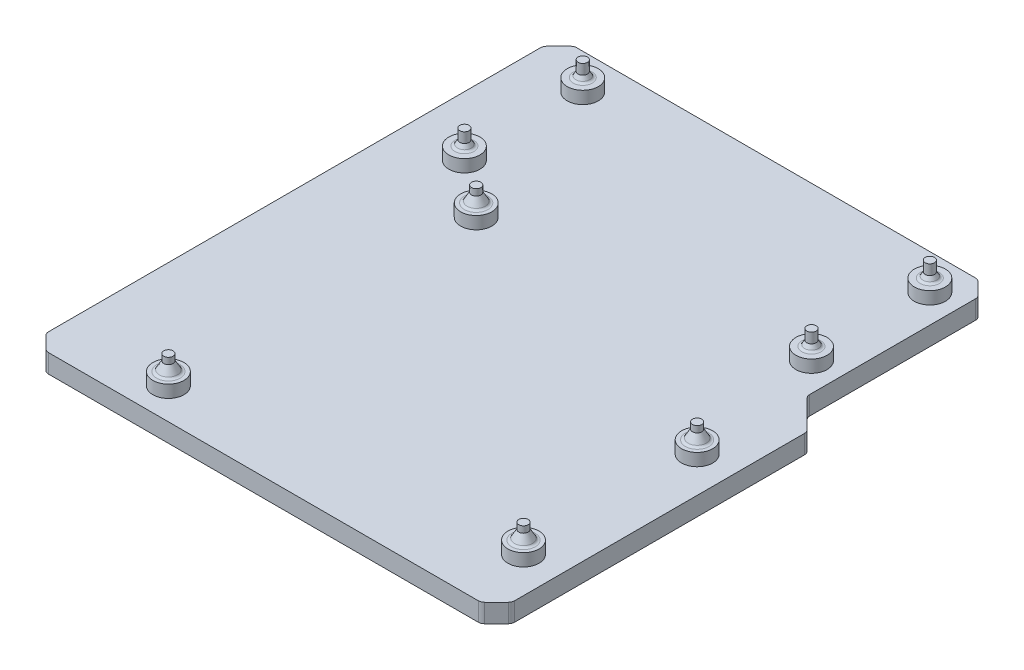
SolidWorks part; units mm, degrees
ref_plane "Front Plane" through (0, 0, 0) normal (0, 0, 1) x (1, 0, 0)
ref_plane "Top Plane" through (0, 0, 0) normal (0, 1, 0) x (1, 0, 0)
ref_plane "Right Plane" through (0, 0, 0) normal (1, 0, 0) x (0, 0, -1)
sketch "Sketch1" plane through (0, 0, 0) normal (0, 1, 0) x (1, 0, 0)
  line L1 (-37.5, 42.5) -> (37.5, 42.5)
  line L2 (-37.5, 42.5) -> (-37.5, -42.5)
  line L3 (-37.5, -42.5) -> (37.5, -42.5)
  line L4 (37.5, 42.5) -> (37.5, -42.5)
  line L5 (-37.5, 42.5) -> (37.5, -42.5) construction
  line L6 (-37.5, -42.5) -> (37.5, 42.5) construction
  point P0 (0, 0)
  dimension "D1" = 85
  dimension "D2" = 75
extrude "Boss-Extrude1" add sketch "Sketch1" along normal blind 3
sketch "Sketch2" plane through (0, 3, 0) normal (0, 1, 0) x (1, 0, 0)
  line L0 (37.5, 42.5) -> (27.93, 42.5) construction
  line L1 (0, -1.65) -> (0, 1.65) construction
  line L2 (-37.5, 42.5) -> (-37.5, -42.5) construction
  line L3 (37.5, 42.5) -> (-37.5, 42.5) construction
  line L4 (27.93, 42.5) -> (27.93, 36.82) construction
  line L5 (37.5, -42.5) -> (37.5, 42.5) construction
  circle A0 centre (27.93, 36.82) radius 2.5
  circle A1 centre (27.93, 17.77) radius 2.5
  circle A3 centre (-27.93, 17.77) radius 2.5
  circle A4 centre (-27.93, 36.82) radius 2.5
  circle A5 centre (-19.05, 10.79) radius 2.5
  circle A6 centre (-20.32, -37.48) radius 2.5
  circle A7 centre (31.75, -4.45) radius 2.5
  circle A8 centre (31.75, -32.4) radius 2.5
  dimension "D3" = 5
  dimension "D5" = 5
  dimension "D7" = 5
  dimension "D10" = 5
  dimension "D13" = 5
  dimension "D16" = 5
  dimension "D1" = 9.57
  dimension "D4" = 19.05
  dimension "D2" = 5.68
  dimension "D6" = 18.45
  dimension "D8" = 6.98
  dimension "D9" = 48.27
  dimension "D11" = 17.18
  dimension "D12" = 5.75
  dimension "D14" = 22.22
  dimension "D15" = 27.95
  dimension "D17" = 5.75
extrude "Boss-Extrude2" add sketch "Sketch2" along normal blind 2
sketch "Sketch3" plane through (0, 5, 0) normal (0, 1, 0) x (1, 0, 0)
  line L0 (0, -2.75) -> (0, 2.75) construction
  line L1 (-27.93, 36.82) -> (-27.93, 17.77) construction
  line L2 (-27.93, 27.295) -> (-10.539, 27.295) construction
  circle A0 centre (-27.93, 36.82) radius 0.75
  circle A1 centre (27.93, 36.82) radius 0.75
  circle A2 centre (27.93, 17.77) radius 0.75
  circle A3 centre (-27.93, 17.77) radius 0.75
  circle A4 centre (-19.05, 10.79) radius 0.75
  circle A5 centre (31.75, -4.45) radius 0.75
  circle A6 centre (-20.32, -37.48) radius 0.75
  circle A7 centre (31.75, -32.4) radius 0.75
  dimension "D1" = 1.5
  dimension "D2" = 1.5
extrude "Boss-Extrude3" add sketch "Sketch3" along normal blind 2.5
chamfer "Chamfer1" distance 0.5 angle 60 4 edges at (27.93, 5, -17.02) (27.93, 5, -37.57) (-27.93, 5, -36.07) (-27.93, 5, -18.52) first distance on face at (27.93, 5, -17.02) first distance on face at (27.93, 5, -37.57) first distance on face at (-27.93, 5, -36.07) first distance on face at (-27.93, 5, -18.52)
chamfer "Chamfer2" distance 0.85 angle 60 4 edges at (31.75, 5, 5.2) (31.75, 5, 33.15) (-20.32, 5, 38.23) (-19.05, 5, -10.04) first distance on face at (31.75, 5, 5.2) first distance on face at (31.75, 5, 33.15) first distance on face at (-20.32, 5, 38.23) first distance on face at (-19.05, 5, -10.04)
fillet "Fillet1" radius 0.5 8 edges at (27.93, 5, -35.57) (27.93, 5, -16.52) (-27.93, 5, -19.02) (-27.93, 5, -38.07) (-19.05, 5, -12.39) (31.75, 5, 34) (-20.32, 5, 35.88) (31.75, 5, 6.05)
sketch "Sketch4" plane through (0, 3, 0) normal (0, 1, 0) x (1, 0, 0)
  line L0 (37.5, -42.5) -> (37.5, 7.5) construction
  line L1 (37.5, -42.5) -> (37.5, 42.5) construction
  line L7 (37.5, 7.5) -> (32.5, 12.5)
  line L8 (32.5, 12.5) -> (32.5, 42.5)
  line L10 (37.5, 42.5) -> (-37.5, 42.5) construction
  line L11 (32.5, 42.5) -> (37.5, 42.5)
  line L12 (37.5, 42.5) -> (37.5, 7.5)
  dimension "D1" = 50
  dimension "D2" = 45
  dimension "D3" = 5
extrude "Cut-Extrude1" cut sketch "Sketch4" against normal up to next
chamfer "Chamfer3" distance 2.5 angle 45 4 edges at (-37.5, 1.5, 42.5) (-37.5, 1.5, -42.5) (37.5, 1.5, 42.5) (32.5, 1.5, -42.5)
fillet "Fillet2" radius 1 10 edges at (-37.5, 1.5, -40) (-35, 1.5, -42.5) (30, 1.5, -42.5) (32.5, 1.5, -40) (32.5, 1.5, -12.5) (37.5, 1.5, -7.5) (37.5, 1.5, 40) (35, 1.5, 42.5) (-37.5, 1.5, 40) (-35, 1.5, 42.5)
equation "\"D1@Sketch2\"=1.93+6.39+1.25"
equation "\"D4@Sketch2\"=16.55+2.5"
equation "\"D2@Sketch2\"=1.93+1.25+2.5"
equation "\"D6@Sketch2\"=3.21+13.65+1.59"
equation "\"D8@Sketch2\"=1.26+0.95+1.93+1.25+1.59"
equation "\"D11@Sketch2\"=12.38+3.21+1.59"
equation "\"D9@Sketch2\"=45.09+2*1.59"
equation "\"D12@Sketch2\"=0.95+1.59+3.21"
equation "\"D14@Sketch2\"=17.45+1.59+1.25+1.93mm"
equation "\"D15@Sketch2\"=24.77+2*1.59"
equation "\"D17@Sketch2\"=0.95+1.59+3.21"
